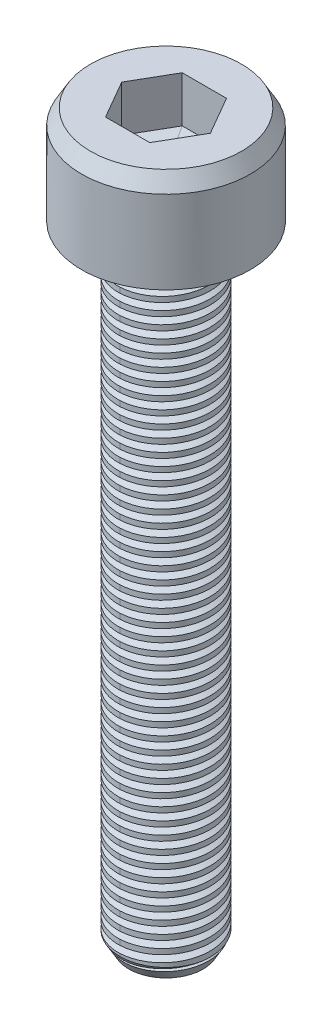
SolidWorks part; units mm, degrees
ref_plane "Front Plane" through (0, 0, 0) normal (0, 0, 1) x (1, 0, 0)
ref_plane "Top Plane" through (0, 0, 0) normal (0, 1, 0) x (1, 0, 0)
ref_plane "Right Plane" through (0, 0, 0) normal (1, 0, 0) x (0, 0, -1)
sketch "Sketch1" plane through (0, 0, 0) normal (0, 1, 0) x (1, 0, 0)
  circle A0 centre (0, 0) radius 2.75
  dimension "D1" = 5.5
extrude "Boss-Extrude1" add sketch "Sketch1" along normal blind 2.7
sketch "Sketch2" plane through (0, 2.7, 0) normal (0, 1, 0) x (1, 0, 0)
  circle A0 centre (0, 0) radius 2.75
  circle A1 centre (0, 0) radius 2.75 construction
  dimension "D1" = 5.5
extrude "Boss-Extrude2" add sketch "Sketch2" along normal blind 0.5 draft 30
sketch "Sketch5" plane through (0, 3.2, 0) normal (0, 1, 0) x (1, 0, 0)
  line L1 (1.4434, 0) -> (0.7217, 1.25)
  line L2 (0.7217, 1.25) -> (-0.7217, 1.25)
  line L3 (-0.7217, 1.25) -> (-1.4434, 0)
  line L4 (-1.4434, 0) -> (-0.7217, -1.25)
  line L5 (-0.7217, -1.25) -> (0.7217, -1.25)
  line L6 (0.7217, -1.25) -> (1.4434, 0)
  circle A0 centre (0, 0) radius 1.25 construction
  circle A1 centre (0, 0) radius 2.4613 construction
  dimension "D1" = 2.5
extrude "Cut-Extrude3" cut sketch "Sketch5" against normal blind 1.5
sketch "Sketch6" plane through (0, 1.7, 0) normal (0, 1, 0) x (1, 0, 0)
  line L0 (1.4434, 0) -> (0.7217, 1.25) construction
  line L1 (1.4434, 0) -> (0.7217, 1.25)
  line L2 (0.7217, 1.25) -> (-0.7217, 1.25)
  line L3 (-0.7217, 1.25) -> (-1.4434, 0)
  line L4 (-1.4434, 0) -> (-0.7217, -1.25)
  line L5 (-0.7217, -1.25) -> (0.7217, -1.25)
  line L6 (0.7217, -1.25) -> (1.4434, 0)
  circle A0 centre (0, 0) radius 1.25 construction
extrude "Cut-Extrude4" cut sketch "Sketch6" against normal blind 0.25 draft 80
sketch "Sketch7" plane through (0, 0, 0) normal (0, -1, 0) x (1, 0, 0)
  circle A0 centre (0, 0) radius 1.5
  circle A1 centre (0, 0) radius 2.75 construction
  dimension "D1" = 3
extrude "Boss-Extrude3" add sketch "Sketch7" along normal blind 20 contours A0
sketch "Sketch8" plane through (0, -20, 0) normal (0, -1, 0) x (1, 0, 0)
  circle A0 centre (0, 0) radius 1.5
  circle A1 centre (0, 0) radius 1.5 construction
  dimension "D1" = 3
extrude "Boss-Extrude4" add sketch "Sketch8" along normal blind 0.5 draft 30
sketch "Sketch9" plane through (0, -20.5, 0) normal (0, -1, 0) x (1, 0, 0)
  circle A0 centre (0, 0) radius 1.5
  circle A1 centre (0, 0) radius 1.2113 construction
  dimension "D1" = 3
curve "Helix/Spiral1" pitch 0.4 height 20 turns 50
sketch "Sketch10" plane through (0, 0, 0) normal (0, 0, 1) x (1, 0, 0)
  line L1 (1.3037, -20.5) -> (1.5981, -20.67)
  line L2 (1.5981, -20.67) -> (1.5981, -20.33)
  line L3 (1.5981, -20.33) -> (1.3037, -20.5)
  circle A0 centre (1.5, -20.5) radius 0.0981 construction
  spline S0 degree 3 poles (1.5, -20.5) (1.5, -20.4917) (1.4219, -20.475) (1.0883, -20.45) (0.589, -20.425) (0, -20.4) (-0.589, -20.375) (-1.0883, -20.35) (-1.4219, -20.325) (-1.5391, -20.3) (-1.4219, -20.275) (-1.0883, -20.25) (-0.589, -20.225) (0, -20.2) (0.589, -20.175) (1.0883, -20.15) (1.4219, -20.125) (1.5391, -20.1) (1.4219, -20.075) (1.0883, -20.05) (0.589, -20.025) (0, -20) (-0.589, -19.975) (-1.0883, -19.95) (-1.4219, -19.925) (-1.5391, -19.9) (-1.4219, -19.875) (-1.0883, -19.85) (-0.589, -19.825) (0, -19.8) (0.589, -19.775) (1.0883, -19.75) (1.4219, -19.725) (1.5391, -19.7) (1.4219, -19.675) (1.0883, -19.65) (0.589, -19.625) (0, -19.6) (-0.589, -19.575) (-1.0883, -19.55) (-1.4219, -19.525) (-1.5391, -19.5) (-1.4219, -19.475) (-1.0883, -19.45) (-0.589, -19.425) (0, -19.4) (0.589, -19.375) (1.0883, -19.35) (1.4219, -19.325) (1.5391, -19.3) (1.4219, -19.275) (1.0883, -19.25) (0.589, -19.225) (0, -19.2) (-0.589, -19.175) (-1.0883, -19.15) (-1.4219, -19.125) (-1.5391, -19.1) (-1.4219, -19.075) (-1.0883, -19.05) (-0.589, -19.025) (0, -19) (0.589, -18.975) (1.0883, -18.95) (1.4219, -18.925) (1.5391, -18.9) (1.4219, -18.875) (1.0883, -18.85) (0.589, -18.825) (0, -18.8) (-0.589, -18.775) (-1.0883, -18.75) (-1.4219, -18.725) (-1.5391, -18.7) (-1.4219, -18.675) (-1.0883, -18.65) (-0.589, -18.625) (0, -18.6) (0.589, -18.575) (1.0883, -18.55) (1.4219, -18.525) (1.5391, -18.5) (1.4219, -18.475) (1.0883, -18.45) (0.589, -18.425) (0, -18.4) (-0.589, -18.375) (-1.0883, -18.35) (-1.4219, -18.325) (-1.5391, -18.3) (-1.4219, -18.275) (-1.0883, -18.25) (-0.589, -18.225) (0, -18.2) (0.589, -18.175) (1.0883, -18.15) (1.4219, -18.125) (1.5391, -18.1) (1.4219, -18.075) (1.0883, -18.05) (0.589, -18.025) (0, -18) (-0.589, -17.975) (-1.0883, -17.95) (-1.4219, -17.925) (-1.5391, -17.9) (-1.4219, -17.875) (-1.0883, -17.85) (-0.589, -17.825) (0, -17.8) (0.589, -17.775) (1.0883, -17.75) (1.4219, -17.725) (1.5391, -17.7) (1.4219, -17.675) (1.0883, -17.65) (0.589, -17.625) (0, -17.6) (-0.589, -17.575) (-1.0883, -17.55) (-1.4219, -17.525) (-1.5391, -17.5) (-1.4219, -17.475) (-1.0883, -17.45) (-0.589, -17.425) (0, -17.4) (0.589, -17.375) (1.0883, -17.35) (1.4219, -17.325) (1.5391, -17.3) (1.4219, -17.275) (1.0883, -17.25) (0.589, -17.225) (0, -17.2) (-0.589, -17.175) (-1.0883, -17.15) (-1.4219, -17.125) (-1.5391, -17.1) (-1.4219, -17.075) (-1.0883, -17.05) (-0.589, -17.025) (0, -17) (0.589, -16.975) (1.0883, -16.95) (1.4219, -16.925) (1.5391, -16.9) (1.4219, -16.875) (1.0883, -16.85) (0.589, -16.825) (0, -16.8) (-0.589, -16.775) (-1.0883, -16.75) (-1.4219, -16.725) (-1.5391, -16.7) (-1.4219, -16.675) (-1.0883, -16.65) (-0.589, -16.625) (0, -16.6) (0.589, -16.575) (1.0883, -16.55) (1.4219, -16.525) (1.5391, -16.5) (1.4219, -16.475) (1.0883, -16.45) (0.589, -16.425) (0, -16.4) (-0.589, -16.375) (-1.0883, -16.35) (-1.4219, -16.325) (-1.5391, -16.3) (-1.4219, -16.275) (-1.0883, -16.25) (-0.589, -16.225) (0, -16.2) (0.589, -16.175) (1.0883, -16.15) (1.4219, -16.125) (1.5391, -16.1) (1.4219, -16.075) (1.0883, -16.05) (0.589, -16.025) (0, -16) (-0.589, -15.975) (-1.0883, -15.95) (-1.4219, -15.925) (-1.5391, -15.9) (-1.4219, -15.875) (-1.0883, -15.85) (-0.589, -15.825) (0, -15.8) (0.589, -15.775) (1.0883, -15.75) (1.4219, -15.725) (1.5391, -15.7) (1.4219, -15.675) (1.0883, -15.65) (0.589, -15.625) (0, -15.6) (-0.589, -15.575) (-1.0883, -15.55) (-1.4219, -15.525) (-1.5391, -15.5) (-1.4219, -15.475) (-1.0883, -15.45) (-0.589, -15.425) (0, -15.4) (0.589, -15.375) (1.0883, -15.35) (1.4219, -15.325) (1.5391, -15.3) (1.4219, -15.275) (1.0883, -15.25) (0.589, -15.225) (0, -15.2) (-0.589, -15.175) (-1.0883, -15.15) (-1.4219, -15.125) (-1.5391, -15.1) (-1.4219, -15.075) (-1.0883, -15.05) (-0.589, -15.025) (0, -15) (0.589, -14.975) (1.0883, -14.95) (1.4219, -14.925) (1.5391, -14.9) (1.4219, -14.875) (1.0883, -14.85) (0.589, -14.825) (0, -14.8) (-0.589, -14.775) (-1.0883, -14.75) (-1.4219, -14.725) (-1.5391, -14.7) (-1.4219, -14.675) (-1.0883, -14.65) (-0.589, -14.625) (0, -14.6) (0.589, -14.575) (1.0883, -14.55) (1.4219, -14.525) (1.5391, -14.5) (1.4219, -14.475) (1.0883, -14.45) (0.589, -14.425) (0, -14.4) (-0.589, -14.375) (-1.0883, -14.35) (-1.4219, -14.325) (-1.5391, -14.3) (-1.4219, -14.275) (-1.0883, -14.25) (-0.589, -14.225) (0, -14.2) (0.589, -14.175) (1.0883, -14.15) (1.4219, -14.125) (1.5391, -14.1) (1.4219, -14.075) (1.0883, -14.05) (0.589, -14.025) (0, -14) (-0.589, -13.975) (-1.0883, -13.95) (-1.4219, -13.925) (-1.5391, -13.9) (-1.4219, -13.875) (-1.0883, -13.85) (-0.589, -13.825) (0, -13.8) (0.589, -13.775) (1.0883, -13.75) (1.4219, -13.725) (1.5391, -13.7) (1.4219, -13.675) (1.0883, -13.65) (0.589, -13.625) (0, -13.6) (-0.589, -13.575) (-1.0883, -13.55) (-1.4219, -13.525) (-1.5391, -13.5) (-1.4219, -13.475) (-1.0883, -13.45) (-0.589, -13.425) (0, -13.4) (0.589, -13.375) (1.0883, -13.35) (1.4219, -13.325) (1.5391, -13.3) (1.4219, -13.275) (1.0883, -13.25) (0.589, -13.225) (0, -13.2) (-0.589, -13.175) (-1.0883, -13.15) (-1.4219, -13.125) (-1.5391, -13.1) (-1.4219, -13.075) (-1.0883, -13.05) (-0.589, -13.025) (0, -13) (0.589, -12.975) (1.0883, -12.95) (1.4219, -12.925) (1.5391, -12.9) (1.4219, -12.875) (1.0883, -12.85) (0.589, -12.825) (0, -12.8) (-0.589, -12.775) (-1.0883, -12.75) (-1.4219, -12.725) (-1.5391, -12.7) (-1.4219, -12.675) (-1.0883, -12.65) (-0.589, -12.625) (0, -12.6) (0.589, -12.575) (1.0883, -12.55) (1.4219, -12.525) (1.5391, -12.5) (1.4219, -12.475) (1.0883, -12.45) (0.589, -12.425) (0, -12.4) (-0.589, -12.375) (-1.0883, -12.35) (-1.4219, -12.325) (-1.5391, -12.3) (-1.4219, -12.275) (-1.0883, -12.25) (-0.589, -12.225) (0, -12.2) (0.589, -12.175) (1.0883, -12.15) (1.4219, -12.125) (1.5391, -12.1) (1.4219, -12.075) (1.0883, -12.05) (0.589, -12.025) (0, -12) (-0.589, -11.975) (-1.0883, -11.95) (-1.4219, -11.925) (-1.5391, -11.9) (-1.4219, -11.875) (-1.0883, -11.85) (-0.589, -11.825) (0, -11.8) (0.589, -11.775) (1.0883, -11.75) (1.4219, -11.725) (1.5391, -11.7) (1.4219, -11.675) (1.0883, -11.65) (0.589, -11.625) (0, -11.6) (-0.589, -11.575) (-1.0883, -11.55) (-1.4219, -11.525) (-1.5391, -11.5) (-1.4219, -11.475) (-1.0883, -11.45) (-0.589, -11.425) (0, -11.4) (0.589, -11.375) (1.0883, -11.35) (1.4219, -11.325) (1.5391, -11.3) (1.4219, -11.275) (1.0883, -11.25) (0.589, -11.225) (0, -11.2) (-0.589, -11.175) (-1.0883, -11.15) (-1.4219, -11.125) (-1.5391, -11.1) (-1.4219, -11.075) (-1.0883, -11.05) (-0.589, -11.025) (0, -11) (0.589, -10.975) (1.0883, -10.95) (1.4219, -10.925) (1.5391, -10.9) (1.4219, -10.875) (1.0883, -10.85) (0.589, -10.825) (0, -10.8) (-0.589, -10.775) (-1.0883, -10.75) (-1.4219, -10.725) (-1.5391, -10.7) (-1.4219, -10.675) (-1.0883, -10.65) (-0.589, -10.625) (0, -10.6) (0.589, -10.575) (1.0883, -10.55) (1.4219, -10.525) (1.5391, -10.5) (1.4219, -10.475) (1.0883, -10.45) (0.589, -10.425) (0, -10.4) (-0.589, -10.375) (-1.0883, -10.35) (-1.4219, -10.325) (-1.5391, -10.3) (-1.4219, -10.275) (-1.0883, -10.25) (-0.589, -10.225) (0, -10.2) (0.589, -10.175) (1.0883, -10.15) (1.4219, -10.125) (1.5391, -10.1) (1.4219, -10.075) (1.0883, -10.05) (0.589, -10.025) (0, -10) (-0.589, -9.975) (-1.0883, -9.95) (-1.4219, -9.925) (-1.5391, -9.9) (-1.4219, -9.875) (-1.0883, -9.85) (-0.589, -9.825) (0, -9.8) (0.589, -9.775) (1.0883, -9.75) (1.4219, -9.725) (1.5391, -9.7) (1.4219, -9.675) (1.0883, -9.65) (0.589, -9.625) (0, -9.6) (-0.589, -9.575) (-1.0883, -9.55) (-1.4219, -9.525) (-1.5391, -9.5) (-1.4219, -9.475) (-1.0883, -9.45) (-0.589, -9.425) (0, -9.4) (0.589, -9.375) (1.0883, -9.35) (1.4219, -9.325) (1.5391, -9.3) (1.4219, -9.275) (1.0883, -9.25) (0.589, -9.225) (0, -9.2) (-0.589, -9.175) (-1.0883, -9.15) (-1.4219, -9.125) (-1.5391, -9.1) (-1.4219, -9.075) (-1.0883, -9.05) (-0.589, -9.025) (0, -9) (0.589, -8.975) (1.0883, -8.95) (1.4219, -8.925) (1.5391, -8.9) (1.4219, -8.875) (1.0883, -8.85) (0.589, -8.825) (0, -8.8) (-0.589, -8.775) (-1.0883, -8.75) (-1.4219, -8.725) (-1.5391, -8.7) (-1.4219, -8.675) (-1.0883, -8.65) (-0.589, -8.625) (0, -8.6) (0.589, -8.575) (1.0883, -8.55) (1.4219, -8.525) (1.5391, -8.5) (1.4219, -8.475) (1.0883, -8.45) (0.589, -8.425) (0, -8.4) (-0.589, -8.375) (-1.0883, -8.35) (-1.4219, -8.325) (-1.5391, -8.3) (-1.4219, -8.275) (-1.0883, -8.25) (-0.589, -8.225) (0, -8.2) (0.589, -8.175) (1.0883, -8.15) (1.4219, -8.125) (1.5391, -8.1) (1.4219, -8.075) (1.0883, -8.05) (0.589, -8.025) (0, -8) (-0.589, -7.975) (-1.0883, -7.95) (-1.4219, -7.925) (-1.5391, -7.9) (-1.4219, -7.875) (-1.0883, -7.85) (-0.589, -7.825) (0, -7.8) (0.589, -7.775) (1.0883, -7.75) (1.4219, -7.725) (1.5391, -7.7) (1.4219, -7.675) (1.0883, -7.65) (0.589, -7.625) (0, -7.6) (-0.589, -7.575) (-1.0883, -7.55) (-1.4219, -7.525) (-1.5391, -7.5) (-1.4219, -7.475) (-1.0883, -7.45) (-0.589, -7.425) (0, -7.4) (0.589, -7.375) (1.0883, -7.35) (1.4219, -7.325) (1.5391, -7.3) (1.4219, -7.275) (1.0883, -7.25) (0.589, -7.225) (0, -7.2) (-0.589, -7.175) (-1.0883, -7.15) (-1.4219, -7.125) (-1.5391, -7.1) (-1.4219, -7.075) (-1.0883, -7.05) (-0.589, -7.025) (0, -7) (0.589, -6.975) (1.0883, -6.95) (1.4219, -6.925) (1.5391, -6.9) (1.4219, -6.875) (1.0883, -6.85) (0.589, -6.825) (0, -6.8) (-0.589, -6.775) (-1.0883, -6.75) (-1.4219, -6.725) (-1.5391, -6.7) (-1.4219, -6.675) (-1.0883, -6.65) (-0.589, -6.625) (0, -6.6) (0.589, -6.575) (1.0883, -6.55) (1.4219, -6.525) (1.5391, -6.5) (1.4219, -6.475) (1.0883, -6.45) (0.589, -6.425) (0, -6.4) (-0.589, -6.375) (-1.0883, -6.35) (-1.4219, -6.325) (-1.5391, -6.3) (-1.4219, -6.275) (-1.0883, -6.25) (-0.589, -6.225) (0, -6.2) (0.589, -6.175) (1.0883, -6.15) (1.4219, -6.125) (1.5391, -6.1) (1.4219, -6.075) (1.0883, -6.05) (0.589, -6.025) (0, -6) (-0.589, -5.975) (-1.0883, -5.95) (-1.4219, -5.925) (-1.5391, -5.9) (-1.4219, -5.875) (-1.0883, -5.85) (-0.589, -5.825) (0, -5.8) (0.589, -5.775) (1.0883, -5.75) (1.4219, -5.725) (1.5391, -5.7) (1.4219, -5.675) (1.0883, -5.65) (0.589, -5.625) (0, -5.6) (-0.589, -5.575) (-1.0883, -5.55) (-1.4219, -5.525) (-1.5391, -5.5) (-1.4219, -5.475) (-1.0883, -5.45) (-0.589, -5.425) (0, -5.4) (0.589, -5.375) (1.0883, -5.35) (1.4219, -5.325) (1.5391, -5.3) (1.4219, -5.275) (1.0883, -5.25) (0.589, -5.225) (0, -5.2) (-0.589, -5.175) (-1.0883, -5.15) (-1.4219, -5.125) (-1.5391, -5.1) (-1.4219, -5.075) (-1.0883, -5.05) (-0.589, -5.025) (0, -5) (0.589, -4.975) (1.0883, -4.95) (1.4219, -4.925) (1.5391, -4.9) (1.4219, -4.875) (1.0883, -4.85) (0.589, -4.825) (0, -4.8) (-0.589, -4.775) (-1.0883, -4.75) (-1.4219, -4.725) (-1.5391, -4.7) (-1.4219, -4.675) (-1.0883, -4.65) (-0.589, -4.625) (0, -4.6) (0.589, -4.575) (1.0883, -4.55) (1.4219, -4.525) (1.5391, -4.5) (1.4219, -4.475) (1.0883, -4.45) (0.589, -4.425) (0, -4.4) (-0.589, -4.375) (-1.0883, -4.35) (-1.4219, -4.325) (-1.5391, -4.3) (-1.4219, -4.275) (-1.0883, -4.25) (-0.589, -4.225) (0, -4.2) (0.589, -4.175) (1.0883, -4.15) (1.4219, -4.125) (1.5391, -4.1) (1.4219, -4.075) (1.0883, -4.05) (0.589, -4.025) (0, -4) (-0.589, -3.975) (-1.0883, -3.95) (-1.4219, -3.925) (-1.5391, -3.9) (-1.4219, -3.875) (-1.0883, -3.85) (-0.589, -3.825) (0, -3.8) (0.589, -3.775) (1.0883, -3.75) (1.4219, -3.725) (1.5391, -3.7) (1.4219, -3.675) (1.0883, -3.65) (0.589, -3.625) (0, -3.6) (-0.589, -3.575) (-1.0883, -3.55) (-1.4219, -3.525) (-1.5391, -3.5) (-1.4219, -3.475) (-1.0883, -3.45) (-0.589, -3.425) (0, -3.4) (0.589, -3.375) (1.0883, -3.35) (1.4219, -3.325) (1.5391, -3.3) (1.4219, -3.275) (1.0883, -3.25) (0.589, -3.225) (0, -3.2) (-0.589, -3.175) (-1.0883, -3.15) (-1.4219, -3.125) (-1.5391, -3.1) (-1.4219, -3.075) (-1.0883, -3.05) (-0.589, -3.025) (0, -3) (0.589, -2.975) (1.0883, -2.95) (1.4219, -2.925) (1.5391, -2.9) (1.4219, -2.875) (1.0883, -2.85) (0.589, -2.825) (0, -2.8) (-0.589, -2.775) (-1.0883, -2.75) (-1.4219, -2.725) (-1.5391, -2.7) (-1.4219, -2.675) (-1.0883, -2.65) (-0.589, -2.625) (0, -2.6) (0.589, -2.575) (1.0883, -2.55) (1.4219, -2.525) (1.5391, -2.5) (1.4219, -2.475) (1.0883, -2.45) (0.589, -2.425) (0, -2.4) (-0.589, -2.375) (-1.0883, -2.35) (-1.4219, -2.325) (-1.5391, -2.3) (-1.4219, -2.275) (-1.0883, -2.25) (-0.589, -2.225) (0, -2.2) (0.589, -2.175) (1.0883, -2.15) (1.4219, -2.125) (1.5391, -2.1) (1.4219, -2.075) (1.0883, -2.05) (0.589, -2.025) (0, -2) (-0.589, -1.975) (-1.0883, -1.95) (-1.4219, -1.925) (-1.5391, -1.9) (-1.4219, -1.875) (-1.0883, -1.85) (-0.589, -1.825) (0, -1.8) (0.589, -1.775) (1.0883, -1.75) (1.4219, -1.725) (1.5391, -1.7) (1.4219, -1.675) (1.0883, -1.65) (0.589, -1.625) (0, -1.6) (-0.589, -1.575) (-1.0883, -1.55) (-1.4219, -1.525) (-1.5391, -1.5) (-1.4219, -1.475) (-1.0883, -1.45) (-0.589, -1.425) (0, -1.4) (0.589, -1.375) (1.0883, -1.35) (1.4219, -1.325) (1.5391, -1.3) (1.4219, -1.275) (1.0883, -1.25) (0.589, -1.225) (0, -1.2) (-0.589, -1.175) (-1.0883, -1.15) (-1.4219, -1.125) (-1.5391, -1.1) (-1.4219, -1.075) (-1.0883, -1.05) (-0.589, -1.025) (0, -1) (0.589, -0.975) (1.0883, -0.95) (1.4219, -0.925) (1.5391, -0.9) (1.4219, -0.875) (1.0883, -0.85) (0.589, -0.825) (0, -0.8) (-0.589, -0.775) (-1.0883, -0.75) (-1.4219, -0.725) (-1.5391, -0.7) (-1.4219, -0.675) (-1.0883, -0.65) (-0.589, -0.625) (0, -0.6) (0.589, -0.575) (1.0883, -0.55) (1.4219, -0.525) (1.5, -0.5083) (1.5, -0.5) knots 0 0 0 0 0.00125 0.0025 0.00375 0.005 0.00625 0.0075 0.00875 0.01 0.01125 0.0125 0.01375 0.015 0.01625 0.0175 0.01875 0.02 0.02125 0.0225 0.02375 0.025 0.02625 0.0275 0.02875 0.03 0.03125 0.0325 0.03375 0.035 0.03625 0.0375 0.03875 0.04 0.04125 0.0425 0.04375 0.045 0.04625 0.0475 0.04875 0.05 0.05125 0.0525 0.05375 0.055 0.05625 0.0575 0.05875 0.06 0.06125 0.0625 0.06375 0.065 0.06625 0.0675 0.06875 0.07 0.07125 0.0725 0.07375 0.075 0.07625 0.0775 0.07875 0.08 0.08125 0.0825 0.08375 0.085 0.08625 0.0875 0.08875 0.09 0.09125 0.0925 0.09375 0.095 0.09625 0.0975 0.09875 0.1 0.10125 0.1025 0.10375 0.105 0.10625 0.1075 0.10875 0.11 0.11125 0.1125 0.11375 0.115 0.11625 0.1175 0.11875 0.12 0.12125 0.1225 0.12375 0.125 0.12625 0.1275 0.12875 0.13 0.13125 0.1325 0.13375 0.135 0.13625 0.1375 0.13875 0.14 0.14125 0.1425 0.14375 0.145 0.14625 0.1475 0.14875 0.15 0.15125 0.1525 0.15375 0.155 0.15625 0.1575 0.15875 0.16 0.16125 0.1625 0.16375 0.165 0.16625 0.1675 0.16875 0.17 0.17125 0.1725 0.17375 0.175 0.17625 0.1775 0.17875 0.18 0.18125 0.1825 0.18375 0.185 0.18625 0.1875 0.18875 0.19 0.19125 0.1925 0.19375 0.195 0.19625 0.1975 0.19875 0.2 0.20125 0.2025 0.20375 0.205 0.20625 0.2075 0.20875 0.21 0.21125 0.2125 0.21375 0.215 0.21625 0.2175 0.21875 0.22 0.22125 0.2225 0.22375 0.225 0.22625 0.2275 0.22875 0.23 0.23125 0.2325 0.23375 0.235 0.23625 0.2375 0.23875 0.24 0.24125 0.2425 0.24375 0.245 0.24625 0.2475 0.24875 0.25 0.25125 0.2525 0.25375 0.255 0.25625 0.2575 0.25875 0.26 0.26125 0.2625 0.26375 0.265 0.26625 0.2675 0.26875 0.27 0.27125 0.2725 0.27375 0.275 0.27625 0.2775 0.27875 0.28 0.28125 0.2825 0.28375 0.285 0.28625 0.2875 0.28875 0.29 0.29125 0.2925 0.29375 0.295 0.29625 0.2975 0.29875 0.3 0.30125 0.3025 0.30375 0.305 0.30625 0.3075 0.30875 0.31 0.31125 0.3125 0.31375 0.315 0.31625 0.3175 0.31875 0.32 0.32125 0.3225 0.32375 0.325 0.32625 0.3275 0.32875 0.33 0.33125 0.3325 0.33375 0.335 0.33625 0.3375 0.33875 0.34 0.34125 0.3425 0.34375 0.345 0.34625 0.3475 0.34875 0.35 0.35125 0.3525 0.35375 0.355 0.35625 0.3575 0.35875 0.36 0.36125 0.3625 0.36375 0.365 0.36625 0.3675 0.36875 0.37 0.37125 0.3725 0.37375 0.375 0.37625 0.3775 0.37875 0.38 0.38125 0.3825 0.38375 0.385 0.38625 0.3875 0.38875 0.39 0.39125 0.3925 0.39375 0.395 0.39625 0.3975 0.39875 0.4 0.40125 0.4025 0.40375 0.405 0.40625 0.4075 0.40875 0.41 0.41125 0.4125 0.41375 0.415 0.41625 0.4175 0.41875 0.42 0.42125 0.4225 0.42375 0.425 0.42625 0.4275 0.42875 0.43 0.43125 0.4325 0.43375 0.435 0.43625 0.4375 0.43875 0.44 0.44125 0.4425 0.44375 0.445 0.44625 0.4475 0.44875 0.45 0.45125 0.4525 0.45375 0.455 0.45625 0.4575 0.45875 0.46 0.46125 0.4625 0.46375 0.465 0.46625 0.4675 0.46875 0.47 0.47125 0.4725 0.47375 0.475 0.47625 0.4775 0.47875 0.48 0.48125 0.4825 0.48375 0.485 0.48625 0.4875 0.48875 0.49 0.49125 0.4925 0.49375 0.495 0.49625 0.4975 0.49875 0.5 0.50125 0.5025 0.50375 0.505 0.50625 0.5075 0.50875 0.51 0.51125 0.5125 0.51375 0.515 0.51625 0.5175 0.51875 0.52 0.52125 0.5225 0.52375 0.525 0.52625 0.5275 0.52875 0.53 0.53125 0.5325 0.53375 0.535 0.53625 0.5375 0.53875 0.54 0.54125 0.5425 0.54375 0.545 0.54625 0.5475 0.54875 0.55 0.55125 0.5525 0.55375 0.555 0.55625 0.5575 0.55875 0.56 0.56125 0.5625 0.56375 0.565 0.56625 0.5675 0.56875 0.57 0.57125 0.5725 0.57375 0.575 0.57625 0.5775 0.57875 0.58 0.58125 0.5825 0.58375 0.585 0.58625 0.5875 0.58875 0.59 0.59125 0.5925 0.59375 0.595 0.59625 0.5975 0.59875 0.6 0.60125 0.6025 0.60375 0.605 0.60625 0.6075 0.60875 0.61 0.61125 0.6125 0.61375 0.615 0.61625 0.6175 0.61875 0.62 0.62125 0.6225 0.62375 0.625 0.62625 0.6275 0.62875 0.63 0.63125 0.6325 0.63375 0.635 0.63625 0.6375 0.63875 0.64 0.64125 0.6425 0.64375 0.645 0.64625 0.6475 0.64875 0.65 0.65125 0.6525 0.65375 0.655 0.65625 0.6575 0.65875 0.66 0.66125 0.6625 0.66375 0.665 0.66625 0.6675 0.66875 0.67 0.67125 0.6725 0.67375 0.675 0.67625 0.6775 0.67875 0.68 0.68125 0.6825 0.68375 0.685 0.68625 0.6875 0.68875 0.69 0.69125 0.6925 0.69375 0.695 0.69625 0.6975 0.69875 0.7 0.70125 0.7025 0.70375 0.705 0.70625 0.7075 0.70875 0.71 0.71125 0.7125 0.71375 0.715 0.71625 0.7175 0.71875 0.72 0.72125 0.7225 0.72375 0.725 0.72625 0.7275 0.72875 0.73 0.73125 0.7325 0.73375 0.735 0.73625 0.7375 0.73875 0.74 0.74125 0.7425 0.74375 0.745 0.74625 0.7475 0.74875 0.75 0.75125 0.7525 0.75375 0.755 0.75625 0.7575 0.75875 0.76 0.76125 0.7625 0.76375 0.765 0.76625 0.7675 0.76875 0.77 0.77125 0.7725 0.77375 0.775 0.77625 0.7775 0.77875 0.78 0.78125 0.7825 0.78375 0.785 0.78625 0.7875 0.78875 0.79 0.79125 0.7925 0.79375 0.795 0.79625 0.7975 0.79875 0.8 0.80125 0.8025 0.80375 0.805 0.80625 0.8075 0.80875 0.81 0.81125 0.8125 0.81375 0.815 0.81625 0.8175 0.81875 0.82 0.82125 0.8225 0.82375 0.825 0.82625 0.8275 0.82875 0.83 0.83125 0.8325 0.83375 0.835 0.83625 0.8375 0.83875 0.84 0.84125 0.8425 0.84375 0.845 0.84625 0.8475 0.84875 0.85 0.85125 0.8525 0.85375 0.855 0.85625 0.8575 0.85875 0.86 0.86125 0.8625 0.86375 0.865 0.86625 0.8675 0.86875 0.87 0.87125 0.8725 0.87375 0.875 0.87625 0.8775 0.87875 0.88 0.88125 0.8825 0.88375 0.885 0.88625 0.8875 0.88875 0.89 0.89125 0.8925 0.89375 0.895 0.89625 0.8975 0.89875 0.9 0.90125 0.9025 0.90375 0.905 0.90625 0.9075 0.90875 0.91 0.91125 0.9125 0.91375 0.915 0.91625 0.9175 0.91875 0.92 0.92125 0.9225 0.92375 0.925 0.92625 0.9275 0.92875 0.93 0.93125 0.9325 0.93375 0.935 0.93625 0.9375 0.93875 0.94 0.94125 0.9425 0.94375 0.945 0.94625 0.9475 0.94875 0.95 0.95125 0.9525 0.95375 0.955 0.95625 0.9575 0.95875 0.96 0.96125 0.9625 0.96375 0.965 0.96625 0.9675 0.96875 0.97 0.97125 0.9725 0.97375 0.975 0.97625 0.9775 0.97875 0.98 0.98125 0.9825 0.98375 0.985 0.98625 0.9875 0.98875 0.99 0.99125 0.9925 0.99375 0.995 0.99625 0.9975 0.99875 1 1 1 1 construction
  dimension "D1" = 0.1963
  dimension "D2" = 1.3037
sweep "Cut-Sweep1" cut profiles "Sketch10" path "Helix/Spiral1" align with end faces yes
